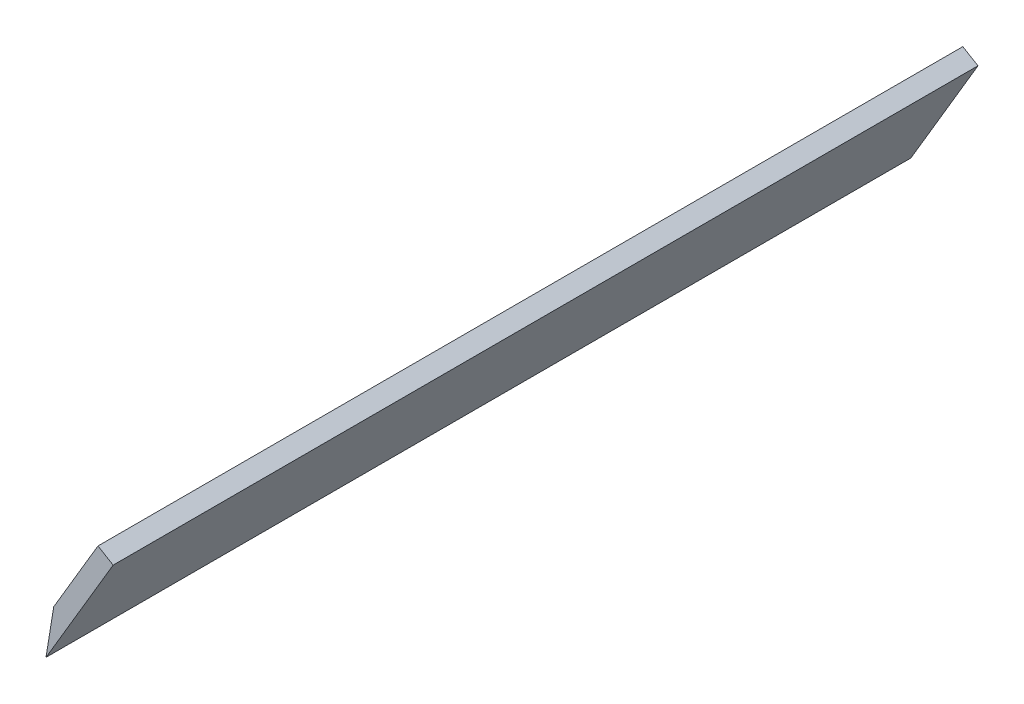
SolidWorks part; units mm, degrees
ref_plane "Plano frontal" through (0, 0, 0) normal (0, 0, 1) x (1, 0, 0)
ref_plane "Plano superior" through (0, 0, 0) normal (0, 1, 0) x (1, 0, 0)
ref_plane "Plano direito" through (0, 0, 0) normal (1, 0, 0) x (0, 0, -1)
sketch "Esboço1" plane through (0, 0, 0) normal (0, 0, 1) x (1, 0, 0)
  line L0 (0, 0) -> (-7.6104, -12.8592)
  line L1 (-7.6104, -12.8592) -> (-9.3316, -11.8406)
  line L2 (-9.3316, -11.8406) -> (-1.7212, 1.0186)
  line L3 (-1.7212, 1.0186) -> (0, 0)
  line L4 (-7.236, -12.6895) -> (-8.5143, -13.2689) construction
  line L5 (0, 0) -> (-7.4601, -12.6052) construction
  line L6 (5.5154, -6.9101) -> (-7.236, -12.6895) construction
  point P2 (-8.5315, -13.287)
  point P8 (-8.523, -13.2733)
  point P9 (-7.6382, -12.872)
  dimension "D1" = 2
extrude "Ressalto-extrusão1" add sketch "Esboço1" along normal up to vertex (98 mm away)
chamfer "Chanfro1" distance 2 angle 45 1 edges at (-9.3316, -11.8406, 49)
sketch "Esboço2" plane through (0, 0, 0) normal (0, 0, -1) x (-1, 0, 0)
  line L0 (6.7357, -7.4545) -> (7.6104, -12.8592)
  line L1 (1.7212, 1.0186) -> (8.3129, -10.1194) construction
  line L2 (7.6104, -12.8592) -> (9.394, -10.1568)
  line L3 (9.394, -10.1568) -> (6.7357, -7.4545)
extrude "Corte-extrusão1" cut sketch "Esboço2" against normal blind 108
